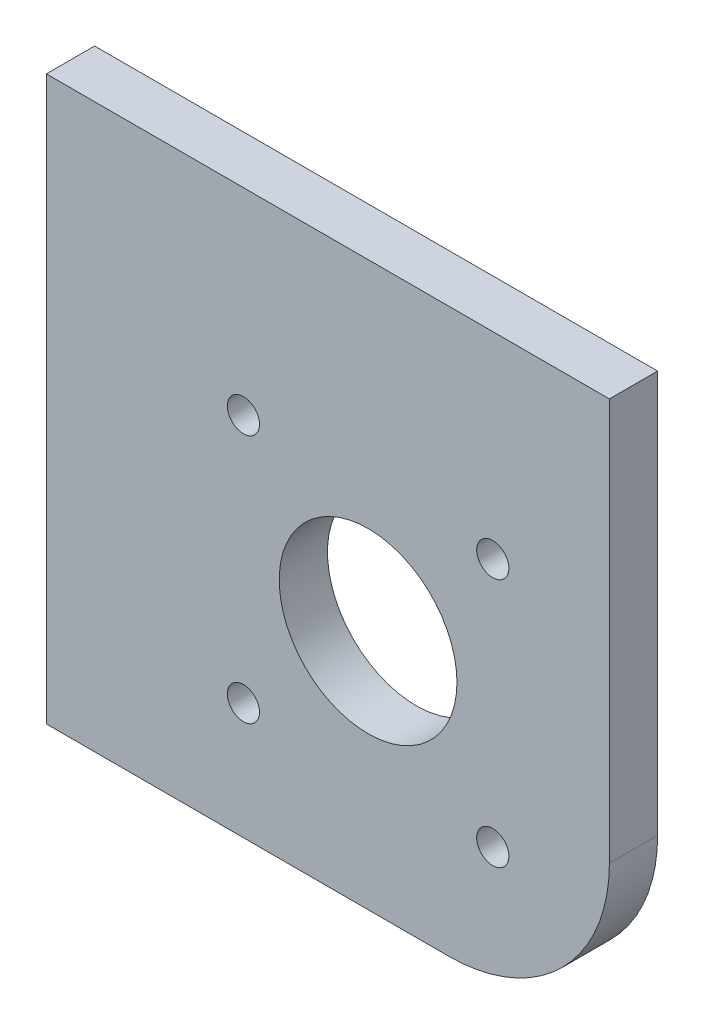
SolidWorks part; units mm, degrees
material "Клен"
ref_plane "Спереди" through (0, 0, 0) normal (0, 0, 1) x (1, 0, 0)
ref_plane "Сверху" through (0, 0, 0) normal (0, 1, 0) x (1, 0, 0)
ref_plane "Справа" through (0, 0, 0) normal (1, 0, 0) x (0, 0, -1)
sketch "Эскиз1" plane through (0, 0, 0) normal (0, 0, 1) x (1, 0, 0)
  line L0 (6, -293.8462) -> (6, -363.8462)
  line L1 (6, -293.8462) -> (6, -593.8462) construction
  line L7 (6, -293.8462) -> (76, -293.8462)
  line L12 (76, -293.8462) -> (76, -343.8462)
  line L14 (56, -363.8462) -> (6, -363.8462)
  arc A0 (76, -343.8462) -> (56, -363.8462) centre (56, -343.8462) cw
  point P7 (0, 0)
  point P9 (44.9121, -438.0873)
  dimension "D2" = 20
  dimension "D1" = 70
extrude "Бобышка-Вытянуть1" add sketch "Эскиз1" against normal blind 6 contours L0 L14 A0 L12 L7
sketch "Эскиз2" plane through (0, 0, 0) normal (0, 0, 1) x (1, 0, 0)
  line L2 (46, -333.8462) -> (46, -382.3555) construction
  line L3 (46, -333.8462) -> (61.8419, -333.8462) construction
  line L4 (76, -293.8462) -> (76, -343.8462) construction
  line L5 (6, -293.8462) -> (76, -293.8462) construction
  circle A0 centre (46, -333.8462) radius 11.05
  circle A1 centre (61.5, -349.3462) radius 2
  circle A2 centre (30.5, -349.3462) radius 2
  circle A3 centre (30.5, -318.3462) radius 2
  circle A4 centre (61.5, -318.3462) radius 2
  dimension "D2" = 22.1
  dimension "D3" = 4
  dimension "D1" = 40
  dimension "D4" = 15.5
  dimension "D5" = 15.5
  dimension "D6" = 30
extrude "Вырез-Вытянуть1" cut sketch "Эскиз2" against normal through all
